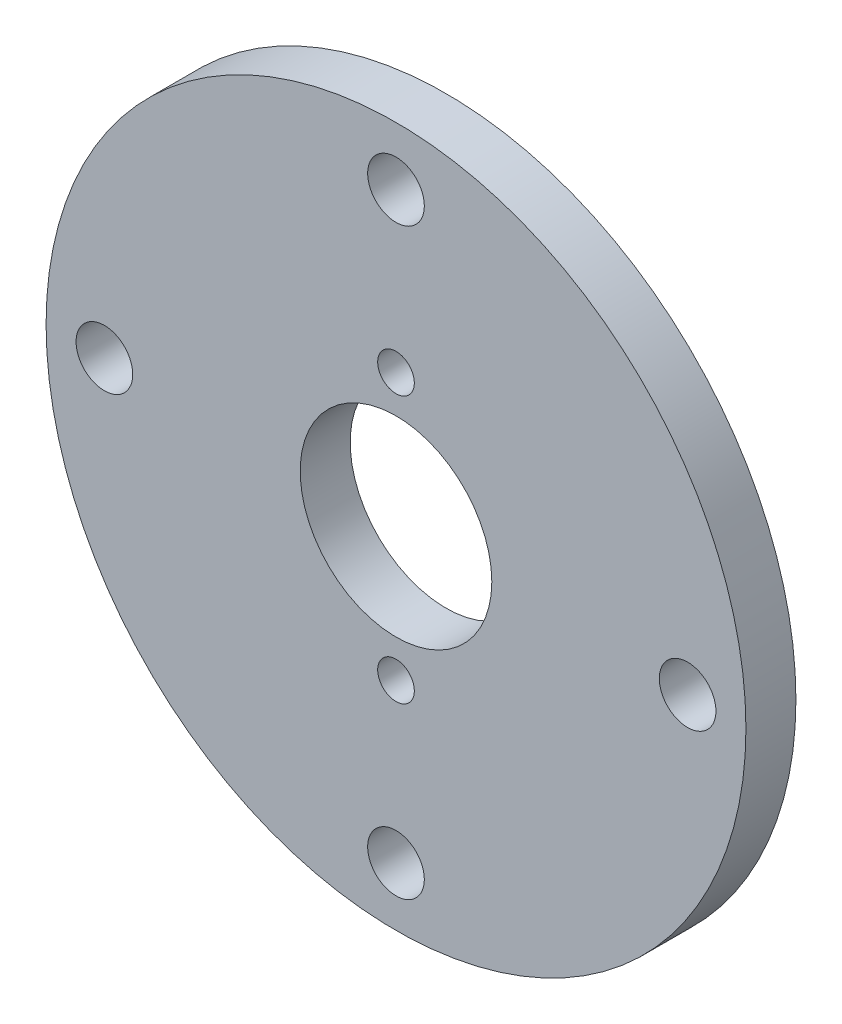
SolidWorks part; units mm, degrees
ref_plane "Front Plane" through (0, 0, 0) normal (0, 0, 1) x (1, 0, 0)
ref_plane "Top Plane" through (0, 0, 0) normal (0, 1, 0) x (1, 0, 0)
ref_plane "Right Plane" through (0, 0, 0) normal (1, 0, 0) x (0, 0, -1)
sketch "Sketch1" plane through (0, 0, 0) normal (0, 0, 1) x (1, 0, 0)
  line L0 (55, 0) -> (-55, 0) construction
  circle A0 centre (0, 8) radius 1.1
  circle A2 centre (0, -8) radius 1.1
  circle A3 centre (0, 0) radius 14
  circle A4 centre (0, 0) radius 5.75
  circle A5 centre (0, 0) radius 21
  circle A6 centre (0, 0) radius 17.5 construction
  circle A7 centre (0, 17.5) radius 1.7
  circle A8 centre (17.5, 0) radius 1.7
  circle A9 centre (0, -17.5) radius 1.7
  circle A10 centre (-17.5, 0) radius 1.7
  dimension "D1" = 2.2
  dimension "D3" = 28
  dimension "D4" = 11.5
  dimension "D5" = 42
  dimension "D7" = 3.4
  dimension "D8" = 3.4
  dimension "D9" = 3.4
  dimension "D10" = 3.4
  dimension "D11" = 3.5
  dimension "D2" = 8
  dimension "D6" = 3.5
extrude "Boss-Extrude1" add sketch "Sketch1" along normal blind 3 contours A5 A10 A9 A8 A7 A3 | A3 A4 A2 A0 region at (-13.604, 0, 0) region at (-20.406, 0, 0)
